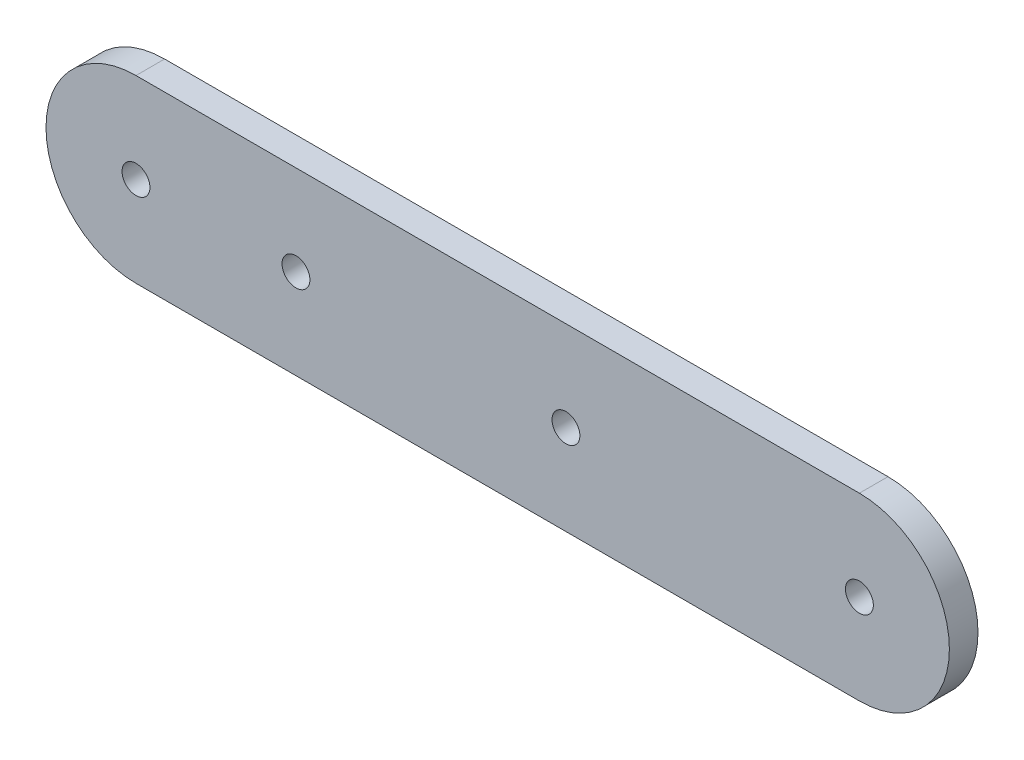
SolidWorks part; units mm, degrees
ref_plane "Front Plane" through (0, 0, 0) normal (0, 0, 1) x (1, 0, 0)
ref_plane "Top Plane" through (0, 0, 0) normal (0, 1, 0) x (1, 0, 0)
ref_plane "Right Plane" through (0, 0, 0) normal (1, 0, 0) x (0, 0, -1)
sketch "Sketch1" plane through (0, 0, 0) normal (0, 0, 1) x (1, 0, 0)
  line L0 (-34.978, 0) -> (34.978, 0) construction
  line L1 (-34.978, 10) -> (45.412, 10)
  line L2 (-34.978, -10) -> (45.412, -10)
  line L3 (45.412, -10) -> (45.412, 10) construction
  arc A0 (-34.978, 10) -> (-34.978, -10) centre (-34.978, 0) ccw
  arc A2 (45.412, -10) -> (45.412, 10) centre (0, 0) ccw
  point P2 (0, 0)
  dimension "D2" = 80.39
  dimension "D3" = 46.5
  dimension "D4" = 10
  dimension "D1" = 20
extrude "Boss-Extrude1" add sketch "Sketch1" along normal mid plane 3.18
sketch "Sketch6" plane through (0, 0, -1.59) normal (0, 0, -1) x (-1, 0, 0)
  line L0 (0, 0) -> (-23.3899, 0) construction
  circle A0 centre (-12.8, 0) radius 1.55
  arc A1 (-45.412, 10) -> (-45.412, -10) centre (0, 0) ccw construction
  dimension "D1" = 3.1
  dimension "D2" = 12.8
extrude "Cut-Extrude3" cut sketch "Sketch6" against normal through all and the other way through all
pattern_linear "LPattern3" count 3 spacing 30 along (-1, 0, 0) of "Cut-Extrude3"
sketch "Sketch7" plane through (0, 0, 1.59) normal (0, 0, 1) x (1, 0, 0)
  line L0 (0, 0) -> (57.5543, 0) construction
  line L1 (29.8, 0) -> (29.8, 14.5305) construction
  circle A1 centre (29.8, 3.5) radius 0.95
  circle A2 centre (29.8, -3.5) radius 0.95
  circle A3 centre (29.8, 0) radius 0.95
  circle A4 centre (12.8, 0) radius 1.55 construction
  dimension "D1" = 17
  dimension "D2" = 1.9
  dimension "D3" = 7
extrude "Cut-Extrude4" [suppressed] cut sketch "Sketch7" against normal through all
pattern_linear "LPattern4" [suppressed] count 2 spacing 14 of bodies 108
sketch "Sketch8" [suppressed] plane through (0, 0, 1.59) normal (0, 0, 1) x (1, 0, 0)
  line L0 (36.8, 7) -> (36.8, 2.3742) construction
  line L1 (33.3, 7) -> (54.2454, 7) construction
  circle A0 centre (33.3, 7) radius 0.95
  circle A2 centre (40.3, 7) radius 0.95
  circle A3 centre (29.8, 3.5) radius 0.95 construction
  circle A4 centre (43.8, 3.5) radius 0.95 construction
  circle A5 centre (36.8, 7) radius 0.95
  dimension "D1" = 3.5
  dimension "D2" = 1.9
  dimension "D3" = 3.5
  dimension "D4" = 3.5
extrude "Cut-Extrude5" [suppressed] cut sketch "Sketch8" against normal through all
mirror "Mirror1" [suppressed] about plane through (0, 0, 0) normal (0, 1, 0)
mirror "Mirror2" [suppressed] about plane through (0, 0, 0) normal (1, 0, 0)
pattern_linear "LPattern5" [suppressed] count 2 spacing 116.18 of bodies 111
sketch "Sketch22" plane through (0, 0, 0) normal (0, 0, 1) x (1, 0, 0)
  line L0 (45.412, 10) -> (45.412, -10)
  arc A0 (45.412, 10) -> (45.412, -10) centre (45.412, 0) cw
  arc A1 (45.412, -10) -> (45.412, 10) centre (0, 0) ccw
  dimension "D1" = 10
  dimension "D2" = 46.5
extrude "Boss-Extrude2" add sketch "Sketch22" along normal mid plane 3.18 contours A1 A0 region at (50.0447, 0, 0)
sketch "Sketch11" plane through (0, 0, 1.59) normal (0, 0, 1) x (1, 0, 0)
  circle A1 centre (-34.978, 0) radius 1.55
  circle A2 centre (45.412, 0) radius 1.55
  dimension "D1" = 3.1
  dimension "D2" = 3.1
extrude "Cut-Extrude7" cut sketch "Sketch11" against normal through all
sketch "Sketch23" [suppressed] plane through (0, 0, 1.59) normal (0, 0, 1) x (1, 0, 0)
  line L0 (-110.588, 10) -> (-110.588, -10)
  line L1 (-110.588, -10) -> (45.412, -10) construction
  arc A1 (-110.588, 10) -> (-110.588, -10) centre (-110.588, 0) ccw
  arc A2 (-110.588, 10) -> (-110.588, -10) centre (-110.588, 0) ccw construction
sketch "Sketch26" [suppressed] plane through (0, 0, -1.59) normal (0, 0, -1) x (-1, 0, 0)
  line L0 (0, 0) -> (-52.9281, 0) construction
  line L1 (-36.8, 7) -> (-36.8, -7) construction
  circle A0 centre (-36.8, 0) radius 10.45
  dimension "D1" = 20.9
extrude "Cut-Extrude11" [suppressed] cut sketch "Sketch26" against normal through all
sketch "Sketch28" [suppressed] plane through (0, 0, -1.59) normal (0, 0, -1) x (-1, 0, 0)
  line L0 (-33.7664, 10) -> (-27.5384, 10)
  line L1 (-33.7664, 10) -> (110.588, 10) construction
  line L2 (-33.7664, -10) -> (-27.5384, -10)
  line L3 (110.588, -10) -> (-33.7664, -10) construction
  line L4 (-39.8336, 10) -> (-45.412, 10)
  line L5 (-45.412, -10) -> (-39.8336, -10)
  arc A0 (-27.5384, 10) -> (-27.5384, -10) centre (-36.8, 0) ccw
  arc A1 (-33.7664, -10) -> (-33.7664, 10) centre (-36.8, 0) ccw construction
  arc A4 (-45.412, 10) -> (-46.2947, 4.3651) centre (0, 0) ccw
  arc A5 (-33.7664, 10) -> (-39.8336, 10) centre (-36.8, 0) ccw
  arc A6 (-46.2947, -4.3651) -> (-45.412, -10) centre (0, 0) ccw
  arc A8 (-39.8336, -10) -> (-33.7664, -10) centre (-36.8, 0) ccw
  arc A9 (-46.2947, 4.3651) -> (-46.2947, -4.3651) centre (-36.8, 0) ccw
  dimension "D1" = 3.18
extrude "Boss-Extrude3" [suppressed] add sketch "Sketch28" against normal blind 3.18
sketch "Sketch29" [suppressed] plane through (0, 0, 1.59) normal (0, 0, 1) x (1, 0, 0)
  circle A0 centre (-41.098, 0) radius 1.55
  dimension "D1" = 3.1
extrude "Cut-Extrude12" [suppressed] cut sketch "Sketch29" against normal through all
sketch "Sketch30" [suppressed] plane through (0, 0, -1.59) normal (0, 0, -1) x (-1, 0, 0)
  circle A0 centre (110.588, 0) radius 1.55
  dimension "D1" = 3.1
extrude "Cut-Extrude13" [suppressed] cut sketch "Sketch30" against normal through all
